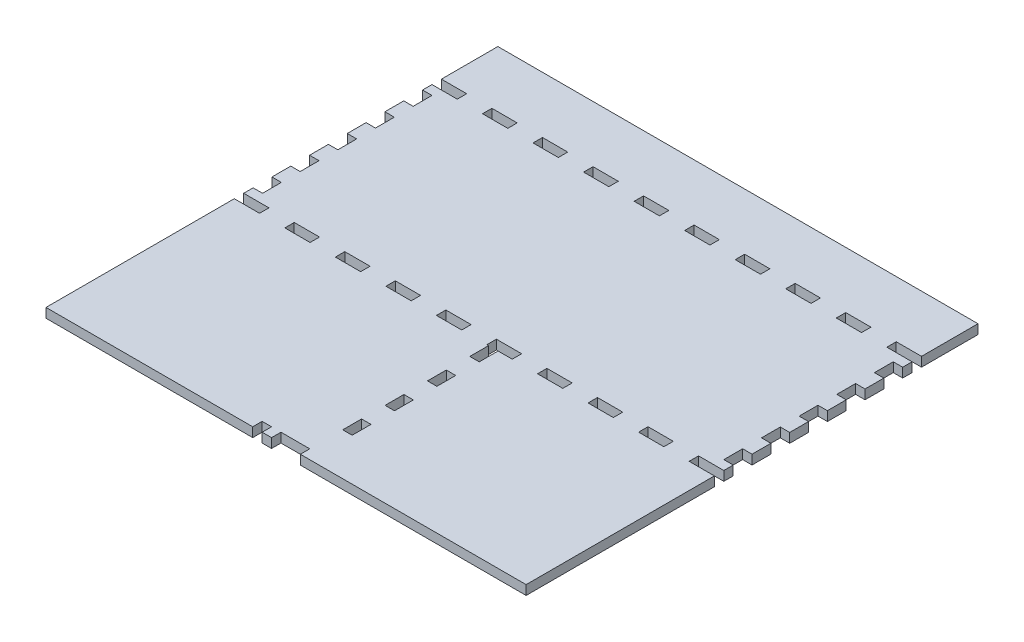
SolidWorks part; units mm, degrees
material "Acrylic (Medium-high impact)"
ref_plane "Front Plane" through (0, 0, 0) normal (0, 0, 1) x (1, 0, 0)
ref_plane "Top Plane" through (0, 0, 0) normal (0, 1, 0) x (1, 0, 0)
ref_plane "Right Plane" through (0, 0, 0) normal (1, 0, 0) x (0, 0, -1)
sketch "Sketch1" plane through (0, 0, 0) normal (0, 1, 0) x (1, 0, 0)
  line L1 (-161.925, 69.85) -> (161.925, 69.85)
  line L2 (-161.925, 69.85) -> (-161.925, -69.85)
  line L3 (-161.925, -69.85) -> (161.925, -69.85)
  line L4 (161.925, 69.85) -> (161.925, -69.85)
  point P4 (-161.925, 0)
  point P6 (0, 69.85)
  dimension "D1" = 139.7
  dimension "D2" = 323.85
extrude "Boss-Extrude1" add sketch "Sketch1" along normal blind 6.35
sketch "Sketch2" plane through (0, 6.35, 0) normal (0, 1, 0) x (1, 0, 0)
  line L0 (161.925, -69.85) -> (161.925, 69.85) construction
  line L1 (-161.925, 69.85) -> (161.925, 69.85)
  line L2 (-161.925, 69.85) -> (-161.925, -69.85)
  line L3 (-161.925, -69.85) -> (161.925, -69.85)
  line L4 (161.925, 69.85) -> (161.925, -69.85)
  line L5 (-161.925, -69.85) -> (161.925, -69.85) construction
  line L7 (-155.575, 63.5) -> (155.575, 63.5)
  line L8 (-155.575, 63.5) -> (-155.575, -63.5)
  line L9 (-155.575, -63.5) -> (155.575, -63.5)
  line L10 (155.575, 63.5) -> (155.575, -63.5)
  point P7 (-155.575, 0)
  point P14 (-161.925, 0)
  point P15 (0, -63.5)
  point P16 (0, -69.85)
  point P17 (155.575, 0)
  point P18 (161.925, 0)
  dimension "D1" = 6.35
  dimension "D2" = 6.35
extrude "Boss-Extrude2" add sketch "Sketch2" along normal blind 298.45
sketch "Sketch3" plane through (0, 0, 69.85) normal (0, 0, 1) x (1, 0, 0)
  line L0 (-50.673, 304.8) -> (-50.673, 0) construction
  line L2 (-155.575, 6.35) -> (155.575, 6.35) construction
  line L4 (-53.975, 283.21) -> (-53.975, 6.35)
  line L5 (-53.975, 6.35) -> (-47.371, 6.35)
  line L6 (-47.371, 292.354) -> (-47.371, 6.35)
  line L7 (-47.371, 292.354) -> (-66.929, 292.354)
  line L9 (-56.515, 285.75) -> (-66.929, 285.75)
  line L10 (-66.929, 292.354) -> (-66.929, 285.75)
  line L11 (-47.371, 101.6) -> (-34.671, 101.6) construction
  line L12 (-161.925, 0) -> (161.925, 0) construction
  line L13 (-37.846, 88.9) -> (-37.846, 101.6) construction
  line L14 (-41.021, 88.9) -> (-34.671, 88.9)
  line L15 (-41.021, 88.9) -> (-41.021, 71.9667)
  line L16 (-41.021, 71.9667) -> (-34.671, 71.9667)
  line L17 (-34.671, 88.9) -> (-34.671, 71.9667)
  line L18 (-41.021, 42.3333) -> (-34.671, 42.3333)
  line L19 (-41.021, 42.3333) -> (-41.021, 59.2667)
  line L20 (-41.021, 59.2667) -> (-34.671, 59.2667)
  line L21 (-34.671, 42.3333) -> (-34.671, 59.2667)
  line L26 (-41.021, 29.6333) -> (-34.671, 29.6333)
  line L27 (-41.021, 29.6333) -> (-41.021, 12.7)
  line L28 (-41.021, 12.7) -> (-34.671, 12.7)
  line L29 (-34.671, 29.6333) -> (-34.671, 12.7)
  line L30 (-37.846, 59.2667) -> (-37.846, 71.9667) construction
  line L31 (-37.846, 29.6333) -> (-37.846, 42.3333) construction
  line L32 (-37.846, 12.7) -> (-37.846, 0) construction
  line L33 (-161.925, 304.8) -> (161.925, 304.8) construction
  line L34 (-155.575, 304.8) -> (-155.575, 6.35) construction
  arc A0 (-53.975, 283.21) -> (-56.515, 285.75) centre (-56.515, 283.21) ccw
  point P5 (-50.673, 6.35)
  dimension "D5" = 2.54
  dimension "D1" = 6.604
  dimension "D2" = 12.954
  dimension "D3" = 6.604
  dimension "D4" = 286.004
  dimension "D6" = 101.6
  dimension "D7" = 12.7
  dimension "D8" = 12.7
  dimension "D9" = 6.35
  dimension "D10" = 101.6
extrude "Door Slot" cut sketch "Sketch3" against normal blind 12.7
sketch "Sketch4" plane through (0, 0, -63.5) normal (0, 0, 1) x (1, 0, 0)
  line L0 (-161.925, 304.8) -> (161.925, 304.8) construction
  line L1 (-73.279, 304.8) -> (-66.929, 304.8)
  line L2 (-73.279, 304.8) -> (-73.279, 6.35)
  line L3 (-73.279, 6.35) -> (-66.929, 6.35)
  line L4 (-66.929, 304.8) -> (-66.929, 6.35)
  line L5 (-44.196, 263.525) -> (-44.196, 247.65) construction
  line L6 (-66.929, 292.354) -> (-66.929, 285.75) construction
  line L7 (-47.371, 304.8) -> (-41.021, 304.8)
  line L8 (-47.371, 304.8) -> (-47.371, 6.35)
  line L9 (-47.371, 6.35) -> (-41.021, 6.35)
  line L10 (-41.021, 304.8) -> (-41.021, 6.35)
  line L11 (155.575, 6.35) -> (-155.575, 6.35) construction
  line L12 (-47.371, 6.35) -> (-47.371, 292.354) construction
  line L13 (-66.929, 304.8) -> (-73.279, 304.8)
  line L14 (-66.929, 304.8) -> (-66.929, 292.1)
  line L15 (-66.929, 292.1) -> (-73.279, 292.1)
  line L16 (-73.279, 304.8) -> (-73.279, 292.1)
  line L17 (-66.929, 276.225) -> (-73.279, 276.225)
  line L18 (-66.929, 276.225) -> (-66.929, 263.525)
  line L19 (-66.929, 263.525) -> (-73.279, 263.525)
  line L20 (-73.279, 276.225) -> (-73.279, 263.525)
  line L21 (-73.279, 6.35) -> (-66.929, 6.35)
  line L22 (-73.279, 6.35) -> (-73.279, 19.05)
  line L23 (-73.279, 19.05) -> (-66.929, 19.05)
  line L24 (-66.929, 6.35) -> (-66.929, 19.05)
  line L25 (-73.279, 34.925) -> (-66.929, 34.925)
  line L26 (-73.279, 34.925) -> (-73.279, 47.625)
  line L27 (-73.279, 47.625) -> (-66.929, 47.625)
  line L28 (-66.929, 34.925) -> (-66.929, 47.625)
  line L29 (-73.279, 92.075) -> (-66.929, 92.075)
  line L30 (-73.279, 92.075) -> (-73.279, 104.775)
  line L31 (-73.279, 104.775) -> (-66.929, 104.775)
  line L32 (-66.929, 92.075) -> (-66.929, 104.775)
  line L33 (-73.279, 149.225) -> (-66.929, 149.225)
  line L34 (-73.279, 149.225) -> (-73.279, 161.925)
  line L35 (-73.279, 161.925) -> (-66.929, 161.925)
  line L36 (-66.929, 149.225) -> (-66.929, 161.925)
  line L37 (-73.279, 177.8) -> (-66.929, 177.8)
  line L38 (-73.279, 177.8) -> (-73.279, 190.5)
  line L39 (-73.279, 190.5) -> (-66.929, 190.5)
  line L40 (-66.929, 177.8) -> (-66.929, 190.5)
  line L41 (-73.279, 206.375) -> (-66.929, 206.375)
  line L42 (-73.279, 206.375) -> (-73.279, 219.075)
  line L43 (-73.279, 219.075) -> (-66.929, 219.075)
  line L44 (-66.929, 206.375) -> (-66.929, 219.075)
  line L45 (-73.279, 234.95) -> (-66.929, 234.95)
  line L46 (-73.279, 234.95) -> (-73.279, 247.65)
  line L47 (-73.279, 247.65) -> (-66.929, 247.65)
  line L48 (-66.929, 234.95) -> (-66.929, 247.65)
  line L49 (-66.929, 133.35) -> (-73.279, 133.35)
  line L50 (-66.929, 133.35) -> (-66.929, 120.65)
  line L51 (-66.929, 120.65) -> (-73.279, 120.65)
  line L52 (-73.279, 133.35) -> (-73.279, 120.65)
  line L53 (-66.929, 76.2) -> (-73.279, 76.2)
  line L54 (-66.929, 76.2) -> (-66.929, 63.5)
  line L55 (-66.929, 63.5) -> (-73.279, 63.5)
  line L56 (-73.279, 76.2) -> (-73.279, 63.5)
  line L57 (-70.104, 304.8) -> (-70.104, 292.1) construction
  line L58 (-70.104, 292.1) -> (-70.104, 276.225) construction
  line L59 (-70.104, 276.225) -> (-70.104, 263.525) construction
  line L60 (-70.104, 247.65) -> (-70.104, 234.95) construction
  line L61 (-70.104, 234.95) -> (-70.104, 219.075) construction
  line L62 (-70.104, 219.075) -> (-70.104, 206.375) construction
  line L63 (-70.104, 206.375) -> (-70.104, 190.5) construction
  line L64 (-70.104, 190.5) -> (-70.104, 177.8) construction
  line L65 (-70.104, 177.8) -> (-70.104, 161.925) construction
  line L66 (-70.104, 161.925) -> (-70.104, 149.225) construction
  line L67 (-70.104, 133.35) -> (-70.104, 120.65) construction
  line L68 (-70.104, 120.65) -> (-70.104, 104.775) construction
  line L69 (-70.104, 104.775) -> (-70.104, 92.075) construction
  line L70 (-70.104, 92.075) -> (-70.104, 76.2) construction
  line L71 (-70.104, 76.2) -> (-70.104, 63.5) construction
  line L72 (-70.104, 63.5) -> (-70.104, 47.625) construction
  line L73 (-70.104, 47.625) -> (-70.104, 34.925) construction
  line L74 (-70.104, 34.925) -> (-70.104, 19.05) construction
  line L75 (-70.104, 19.05) -> (-70.104, 6.35) construction
  line L76 (-70.104, 149.225) -> (-70.104, 133.35) construction
  line L77 (-70.104, 263.525) -> (-70.104, 247.65) construction
  line L78 (-57.15, 304.8) -> (-57.15, 0) construction
  line L79 (161.925, 304.8) -> (-161.925, 304.8) construction
  line L80 (161.925, 0) -> (-161.925, 0) construction
  line L81 (-57.15, 8.3493) -> (-47.371, 8.3493) construction
  line L82 (-57.15, 8.3493) -> (-66.929, 8.3493) construction
  line L83 (-44.196, 149.225) -> (-44.196, 133.35) construction
  line L84 (-44.196, 19.05) -> (-44.196, 6.35) construction
  line L85 (-44.196, 34.925) -> (-44.196, 19.05) construction
  line L86 (-44.196, 47.625) -> (-44.196, 34.925) construction
  line L87 (-44.196, 63.5) -> (-44.196, 47.625) construction
  line L88 (-44.196, 76.2) -> (-44.196, 63.5) construction
  line L89 (-44.196, 92.075) -> (-44.196, 76.2) construction
  line L90 (-44.196, 104.775) -> (-44.196, 92.075) construction
  line L91 (-44.196, 120.65) -> (-44.196, 104.775) construction
  line L92 (-44.196, 133.35) -> (-44.196, 120.65) construction
  line L93 (-44.196, 161.925) -> (-44.196, 149.225) construction
  line L94 (-44.196, 177.8) -> (-44.196, 161.925) construction
  line L95 (-44.196, 190.5) -> (-44.196, 177.8) construction
  line L96 (-44.196, 206.375) -> (-44.196, 190.5) construction
  line L97 (-44.196, 219.075) -> (-44.196, 206.375) construction
  line L98 (-44.196, 234.95) -> (-44.196, 219.075) construction
  line L99 (-44.196, 247.65) -> (-44.196, 234.95) construction
  line L100 (-44.196, 276.225) -> (-44.196, 263.525) construction
  line L101 (-44.196, 292.1) -> (-44.196, 276.225) construction
  line L102 (-44.196, 304.8) -> (-44.196, 292.1) construction
  line L103 (-41.021, 76.2) -> (-41.021, 63.5)
  line L104 (-47.371, 63.5) -> (-41.021, 63.5)
  line L105 (-47.371, 76.2) -> (-47.371, 63.5)
  line L106 (-47.371, 76.2) -> (-41.021, 76.2)
  line L107 (-41.021, 133.35) -> (-41.021, 120.65)
  line L108 (-47.371, 120.65) -> (-41.021, 120.65)
  line L109 (-47.371, 133.35) -> (-47.371, 120.65)
  line L110 (-47.371, 133.35) -> (-41.021, 133.35)
  line L111 (-47.371, 234.95) -> (-47.371, 247.65)
  line L112 (-41.021, 247.65) -> (-47.371, 247.65)
  line L113 (-41.021, 234.95) -> (-41.021, 247.65)
  line L114 (-41.021, 234.95) -> (-47.371, 234.95)
  line L115 (-47.371, 206.375) -> (-47.371, 219.075)
  line L116 (-41.021, 219.075) -> (-47.371, 219.075)
  line L117 (-41.021, 206.375) -> (-41.021, 219.075)
  line L118 (-41.021, 206.375) -> (-47.371, 206.375)
  line L119 (-47.371, 177.8) -> (-47.371, 190.5)
  line L120 (-41.021, 190.5) -> (-47.371, 190.5)
  line L121 (-41.021, 177.8) -> (-41.021, 190.5)
  line L122 (-41.021, 177.8) -> (-47.371, 177.8)
  line L123 (-47.371, 149.225) -> (-47.371, 161.925)
  line L124 (-41.021, 161.925) -> (-47.371, 161.925)
  line L125 (-41.021, 149.225) -> (-41.021, 161.925)
  line L126 (-41.021, 149.225) -> (-47.371, 149.225)
  line L127 (-47.371, 92.075) -> (-47.371, 104.775)
  line L128 (-41.021, 104.775) -> (-47.371, 104.775)
  line L129 (-41.021, 92.075) -> (-41.021, 104.775)
  line L130 (-41.021, 92.075) -> (-47.371, 92.075)
  line L131 (-47.371, 34.925) -> (-47.371, 47.625)
  line L132 (-41.021, 47.625) -> (-47.371, 47.625)
  line L133 (-41.021, 34.925) -> (-41.021, 47.625)
  line L134 (-41.021, 34.925) -> (-47.371, 34.925)
  line L135 (-47.371, 6.35) -> (-47.371, 19.05)
  line L136 (-41.021, 19.05) -> (-47.371, 19.05)
  line L137 (-41.021, 6.35) -> (-41.021, 19.05)
  line L138 (-41.021, 6.35) -> (-47.371, 6.35)
  line L139 (-41.021, 276.225) -> (-41.021, 263.525)
  line L140 (-47.371, 263.525) -> (-41.021, 263.525)
  line L141 (-47.371, 276.225) -> (-47.371, 263.525)
  line L142 (-47.371, 276.225) -> (-41.021, 276.225)
  line L143 (-41.021, 304.8) -> (-41.021, 292.1)
  line L144 (-47.371, 292.1) -> (-41.021, 292.1)
  line L145 (-47.371, 304.8) -> (-47.371, 292.1)
  line L146 (-47.371, 304.8) -> (-41.021, 304.8)
  line L147 (-47.371, 304.8) -> (-47.371, 6.35)
  line L148 (-41.021, 6.35) -> (-47.371, 6.35)
  line L149 (-41.021, 304.8) -> (-41.021, 6.35)
  line L150 (-41.021, 304.8) -> (-47.371, 304.8)
  point P14 (-66.929, 289.052)
  dimension "D1" = 6.35
  dimension "D2" = 12.7
extrude "Door Guide Holes" cut sketch "Sketch4" against normal up to next contours L17 L4 L15 L2 | L2 L47 L4 L19 | L45 L2 L43 L4 | L41 L2 L39 L4 | L37 L2 L35 L4 | L49 L4 L33 L2 | L4 L51 L2 L31 | L53 L4 L29 L2 | L4 L55 L2 L27 | L25 L2 L23 L4 region at (-70.104, 284.1625, -63.5) region at (-70.104, 255.5875, -63.5) region at (-70.104, 227.0125, -63.5) region at (-70.104, 198.4375, -63.5) region at (-70.104, 169.8625, -63.5) region at (-70.104, 141.2875, -63.5) region at (-70.104, 112.7125, -63.5) region at (-70.104, 84.1375, -63.5) region at (-70.104, 55.5625, -63.5) region at (-70.104, 26.9875, -63.5)
ref_plane "Plane1" through (-57.15, 0, 0) normal (-1, 0, 0) x (0, 0, 1)
mirror "Mirror1" about plane through (-57.15, 0, 0) normal (-1, 0, 0) of "Door Guide Holes"
sketch "Lever Holes" plane through (0, 0, 69.85) normal (0, 0, 1) x (1, 0, 0)
  line L0 (49.276, 31.75) -> (58.928, 31.75)
  line L1 (49.276, 31.75) -> (49.276, 25.4)
  line L2 (49.276, 25.4) -> (58.928, 25.4)
  line L3 (58.928, 31.75) -> (58.928, 25.4)
  line L4 (36.1315, 19.05) -> (42.4815, 19.05)
  line L5 (36.1315, 19.05) -> (36.1315, 12.7)
  line L6 (36.1315, 12.7) -> (42.4815, 12.7)
  line L7 (42.4815, 19.05) -> (42.4815, 12.7)
  line L8 (65.7225, 19.05) -> (72.0725, 19.05)
  line L9 (65.7225, 19.05) -> (65.7225, 12.7)
  line L10 (65.7225, 12.7) -> (72.0725, 12.7)
  line L11 (72.0725, 19.05) -> (72.0725, 12.7)
  line L12 (42.4815, 15.875) -> (65.7225, 15.875) construction
  line L13 (-161.925, 0) -> (161.925, 0) construction
  line L14 (-47.371, 6.35) -> (155.575, 6.35) construction
  line L15 (155.575, 6.35) -> (-155.575, 6.35) construction
  point P12 (54.102, 15.875)
  point P13 (54.102, 25.4)
  point P24 (54.102, 6.35)
  dimension "D1" = 9.652
  dimension "D2" = 6.35
  dimension "D3" = 6.35
  dimension "D4" = 6.35
  dimension "D5" = 23.241
  dimension "D6" = 25.4
  dimension "D7" = 12.7
extrude "Cut-Extrude1" cut sketch "Lever Holes" against normal through all
sketch "Sketch7" plane through (161.925, 0, 0) normal (1, 0, 0) x (0, 0, -1)
  line L0 (-37.211, 92.583) -> (37.211, 92.583)
  line L1 (-37.211, 92.583) -> (-37.211, 18.161)
  line L2 (-37.211, 18.161) -> (37.211, 18.161)
  line L3 (37.211, 92.583) -> (37.211, 18.161)
  line L4 (-69.85, 0) -> (69.85, 0) construction
  circle A0 centre (0, 55.372) radius 26.9875
  circle A1 centre (-37.211, 92.583) radius 3.175
  circle A2 centre (37.211, 92.583) radius 3.175
  circle A3 centre (-37.211, 18.161) radius 3.175
  circle A4 centre (37.211, 18.161) radius 3.175
  point P9 (0, 18.161)
  point P10 (-37.211, 55.372)
  dimension "D3" = 53.975
  dimension "D4" = 6.35
  dimension "D1" = 74.422
  dimension "D2" = 55.372
extrude "Cut-Extrude2" cut sketch "Sketch7" against normal up to next contours A0 | L0 A1 L1 | L1 A1 L0 | L3 A2 L0 | L0 A2 L3 | L2 A3 L1 | L1 A3 L2 | L2 A4 L3 | L3 A4 L2 region at (161.925, 93.0322, 37.6602) region at (161.925, 91.2355, 35.8635) region at (161.925, 93.0322, -37.6602) region at (161.925, 91.2355, -35.8635) region at (161.925, 19.5085, 35.8635) region at (161.925, 17.7118, 37.6602) region at (161.925, 17.7118, -37.6602) region at (161.925, 19.5085, -35.8635) region at (161.925, 55.372, 0)
sketch "Sketch8" plane through (-161.925, 0, 0) normal (-1, 0, 0) x (0, 0, 1)
  line L0 (-69.85, 0) -> (69.85, 0) construction
  circle A0 centre (0, 19.05) radius 3.175
  point P6 (0, 0)
  dimension "D1" = 6.35
  dimension "D2" = 19.05
extrude "Cut-Extrude3" cut sketch "Sketch8" against normal up to next
sketch "Sketch10" plane through (0, 0, 0) normal (0, -1, 0) x (1, 0, 0)
  line L0 (-155.575, 63.5) -> (155.575, 63.5) construction
  line L1 (-161.925, 69.85) -> (-144.8803, 69.85)
  line L2 (-161.925, 69.85) -> (-161.925, 63.5)
  line L3 (-161.925, 63.5) -> (-144.8803, 63.5)
  line L4 (-144.8803, 69.85) -> (-144.8803, 63.5)
  line L5 (-144.8803, 69.85) -> (-127.8355, 69.85)
  line L6 (-144.8803, 69.85) -> (-144.8803, 63.5)
  line L7 (-144.8803, 63.5) -> (-127.8355, 63.5)
  line L8 (-127.8355, 69.85) -> (-127.8355, 63.5)
  line L9 (-127.8355, 69.85) -> (-110.7908, 69.85)
  line L10 (-127.8355, 69.85) -> (-127.8355, 63.5)
  line L11 (-127.8355, 63.5) -> (-110.7908, 63.5)
  line L12 (-110.7908, 69.85) -> (-110.7908, 63.5)
  line L13 (-110.7908, 69.85) -> (-93.7461, 69.85)
  line L14 (-110.7908, 69.85) -> (-110.7908, 63.5)
  line L15 (-110.7908, 63.5) -> (-93.7461, 63.5)
  line L16 (-93.7461, 69.85) -> (-93.7461, 63.5)
  line L17 (-161.925, 69.85) -> (161.925, 69.85) construction
  line L18 (-66.929, 63.5) -> (-47.371, 63.5) construction
  line L19 (-93.7461, 69.85) -> (-76.7013, 69.85)
  line L20 (-93.7461, 69.85) -> (-93.7461, 63.5)
  line L21 (-93.7461, 63.5) -> (-76.7013, 63.5)
  line L22 (-76.7013, 69.85) -> (-76.7013, 63.5)
  line L23 (-76.7013, 69.85) -> (-59.6566, 69.85)
  line L24 (-76.7013, 69.85) -> (-76.7013, 63.5)
  line L25 (-76.7013, 63.5) -> (-59.6566, 63.5)
  line L26 (-59.6566, 69.85) -> (-59.6566, 63.5)
  line L27 (-59.6566, 69.85) -> (-42.6118, 69.85)
  line L28 (-59.6566, 69.85) -> (-59.6566, 63.5)
  line L29 (-59.6566, 63.5) -> (-42.6118, 63.5)
  line L30 (-42.6118, 69.85) -> (-42.6118, 63.5)
  line L31 (-42.6118, 69.85) -> (-25.5671, 69.85)
  line L32 (-42.6118, 69.85) -> (-42.6118, 63.5)
  line L33 (-42.6118, 63.5) -> (-25.5671, 63.5)
  line L34 (-25.5671, 69.85) -> (-25.5671, 63.5)
  line L36 (-25.5671, 69.85) -> (-8.5224, 69.85)
  line L37 (-25.5671, 69.85) -> (-25.5671, 63.5)
  line L38 (-25.5671, 63.5) -> (-8.5224, 63.5)
  line L39 (-8.5224, 69.85) -> (-8.5224, 63.5)
  line L40 (-8.5224, 69.85) -> (8.5224, 69.85)
  line L41 (-8.5224, 69.85) -> (-8.5224, 63.5)
  line L42 (-8.5224, 63.5) -> (8.5224, 63.5)
  line L43 (8.5224, 69.85) -> (8.5224, 63.5)
  line L44 (8.5224, 69.85) -> (25.5671, 69.85)
  line L45 (8.5224, 69.85) -> (8.5224, 63.5)
  line L46 (8.5224, 63.5) -> (25.5671, 63.5)
  line L47 (25.5671, 69.85) -> (25.5671, 63.5)
  line L48 (25.5671, 69.85) -> (42.6118, 69.85)
  line L49 (25.5671, 69.85) -> (25.5671, 63.5)
  line L50 (25.5671, 63.5) -> (42.6118, 63.5)
  line L51 (42.6118, 69.85) -> (42.6118, 63.5)
  line L52 (42.6118, 69.85) -> (59.6566, 69.85)
  line L53 (42.6118, 69.85) -> (42.6118, 63.5)
  line L54 (42.6118, 63.5) -> (59.6566, 63.5)
  line L55 (59.6566, 69.85) -> (59.6566, 63.5)
  line L56 (59.6566, 69.85) -> (76.7013, 69.85)
  line L57 (59.6566, 69.85) -> (59.6566, 63.5)
  line L58 (59.6566, 63.5) -> (76.7013, 63.5)
  line L59 (76.7013, 69.85) -> (76.7013, 63.5)
  line L60 (76.7013, 69.85) -> (93.7461, 69.85)
  line L61 (76.7013, 69.85) -> (76.7013, 63.5)
  line L62 (76.7013, 63.5) -> (93.7461, 63.5)
  line L63 (93.7461, 69.85) -> (93.7461, 63.5)
  line L64 (93.7461, 69.85) -> (110.7908, 69.85)
  line L65 (93.7461, 69.85) -> (93.7461, 63.5)
  line L66 (93.7461, 63.5) -> (110.7908, 63.5)
  line L67 (110.7908, 69.85) -> (110.7908, 63.5)
  line L68 (110.7908, 69.85) -> (127.8355, 69.85)
  line L69 (110.7908, 69.85) -> (110.7908, 63.5)
  line L70 (110.7908, 63.5) -> (127.8355, 63.5)
  line L71 (127.8355, 69.85) -> (127.8355, 63.5)
  line L72 (127.8355, 69.85) -> (144.8803, 69.85)
  line L73 (127.8355, 69.85) -> (127.8355, 63.5)
  line L74 (127.8355, 63.5) -> (144.8803, 63.5)
  line L75 (144.8803, 69.85) -> (144.8803, 63.5)
  line L76 (-155.575, -63.5) -> (-155.575, 63.5) construction
  line L77 (-161.925, 69.85) -> (-155.575, 69.85)
  line L78 (-161.925, 69.85) -> (-161.925, 57.15)
  line L79 (-161.925, 57.15) -> (-155.575, 57.15)
  line L80 (-155.575, 69.85) -> (-155.575, 57.15)
  line L82 (-161.925, 57.15) -> (-155.575, 57.15)
  line L83 (-161.925, 57.15) -> (-161.925, 44.45)
  line L84 (-161.925, 44.45) -> (-155.575, 44.45)
  line L85 (-155.575, 57.15) -> (-155.575, 44.45)
  line L86 (-161.925, 44.45) -> (-155.575, 44.45)
  line L87 (-161.925, 44.45) -> (-161.925, 31.75)
  line L88 (-161.925, 31.75) -> (-155.575, 31.75)
  line L89 (-155.575, 44.45) -> (-155.575, 31.75)
  line L90 (-161.925, 31.75) -> (-155.575, 31.75)
  line L91 (-161.925, 31.75) -> (-161.925, 19.05)
  line L92 (-161.925, 19.05) -> (-155.575, 19.05)
  line L93 (-155.575, 31.75) -> (-155.575, 19.05)
  line L94 (-161.925, 19.05) -> (-155.575, 19.05)
  line L95 (-161.925, 19.05) -> (-161.925, 6.35)
  line L96 (-161.925, 6.35) -> (-155.575, 6.35)
  line L97 (-155.575, 19.05) -> (-155.575, 6.35)
  line L98 (-161.925, 6.35) -> (-155.575, 6.35)
  line L99 (-161.925, 6.35) -> (-161.925, -6.35)
  line L100 (-161.925, -6.35) -> (-155.575, -6.35)
  line L101 (-155.575, 6.35) -> (-155.575, -6.35)
  line L102 (-161.925, -6.35) -> (-155.575, -6.35)
  line L103 (-161.925, -6.35) -> (-161.925, -19.05)
  line L104 (-161.925, -19.05) -> (-155.575, -19.05)
  line L105 (-155.575, -6.35) -> (-155.575, -19.05)
  line L106 (-161.925, -19.05) -> (-155.575, -19.05)
  line L107 (-161.925, -19.05) -> (-161.925, -31.75)
  line L108 (-161.925, -31.75) -> (-155.575, -31.75)
  line L109 (-155.575, -19.05) -> (-155.575, -31.75)
  line L110 (-161.925, -31.75) -> (-155.575, -31.75)
  line L111 (-161.925, -31.75) -> (-161.925, -44.45)
  line L112 (-161.925, -44.45) -> (-155.575, -44.45)
  line L113 (-155.575, -31.75) -> (-155.575, -44.45)
  line L114 (-161.925, -44.45) -> (-155.575, -44.45)
  line L115 (-161.925, -44.45) -> (-161.925, -57.15)
  line L116 (-161.925, -57.15) -> (-155.575, -57.15)
  line L117 (-155.575, -44.45) -> (-155.575, -57.15)
  line L118 (161.925, 69.85) -> (161.925, -69.85) construction
  line L119 (144.8803, 69.85) -> (161.925, 69.85)
  line L120 (144.8803, 69.85) -> (144.8803, 63.5)
  line L121 (144.8803, 63.5) -> (161.925, 63.5)
  line L122 (161.925, 69.85) -> (161.925, 63.5)
  line L123 (161.925, -69.85) -> (-161.925, -69.85) construction
  line L124 (-161.925, -57.15) -> (-155.575, -57.15)
  line L125 (-161.925, -57.15) -> (-161.925, -69.85)
  line L126 (-161.925, -69.85) -> (-155.575, -69.85)
  line L127 (-155.575, -57.15) -> (-155.575, -69.85)
  line L128 (55, 0) -> (-55, 0) construction
  line L129 (161.925, -69.85) -> (161.925, -63.5)
  line L130 (144.8803, -63.5) -> (161.925, -63.5)
  line L131 (144.8803, -69.85) -> (161.925, -69.85)
  line L132 (144.8803, -69.85) -> (144.8803, -63.5)
  line L133 (127.8355, -63.5) -> (144.8803, -63.5)
  line L134 (127.8355, -69.85) -> (144.8803, -69.85)
  line L135 (127.8355, -69.85) -> (127.8355, -63.5)
  line L136 (110.7908, -63.5) -> (127.8355, -63.5)
  line L137 (110.7908, -69.85) -> (127.8355, -69.85)
  line L138 (110.7908, -69.85) -> (110.7908, -63.5)
  line L139 (93.7461, -63.5) -> (110.7908, -63.5)
  line L140 (93.7461, -69.85) -> (110.7908, -69.85)
  line L141 (93.7461, -69.85) -> (93.7461, -63.5)
  line L142 (76.7013, -63.5) -> (93.7461, -63.5)
  line L143 (76.7013, -69.85) -> (93.7461, -69.85)
  line L144 (59.6566, -63.5) -> (76.7013, -63.5)
  line L145 (76.7013, -69.85) -> (76.7013, -63.5)
  line L146 (59.6566, -69.85) -> (76.7013, -69.85)
  line L147 (59.6566, -69.85) -> (59.6566, -63.5)
  line L148 (42.6118, -63.5) -> (59.6566, -63.5)
  line L149 (42.6118, -69.85) -> (59.6566, -69.85)
  line L150 (42.6118, -69.85) -> (42.6118, -63.5)
  line L151 (25.5671, -63.5) -> (42.6118, -63.5)
  line L152 (25.5671, -69.85) -> (42.6118, -69.85)
  line L153 (25.5671, -69.85) -> (25.5671, -63.5)
  line L154 (8.5224, -69.85) -> (25.5671, -69.85)
  line L155 (8.5224, -63.5) -> (25.5671, -63.5)
  line L156 (8.5224, -69.85) -> (8.5224, -63.5)
  line L157 (-8.5224, -63.5) -> (8.5224, -63.5)
  line L158 (-8.5224, -69.85) -> (8.5224, -69.85)
  line L159 (-25.5671, -63.5) -> (-8.5224, -63.5)
  line L160 (-8.5224, -69.85) -> (-8.5224, -63.5)
  line L161 (-25.5671, -69.85) -> (-8.5224, -69.85)
  line L162 (-25.5671, -69.85) -> (-25.5671, -63.5)
  line L163 (-42.6118, -63.5) -> (-25.5671, -63.5)
  line L164 (-42.6118, -69.85) -> (-25.5671, -69.85)
  line L165 (-42.6118, -69.85) -> (-42.6118, -63.5)
  line L166 (-59.6566, -63.5) -> (-42.6118, -63.5)
  line L167 (-59.6566, -69.85) -> (-42.6118, -69.85)
  line L168 (-59.6566, -69.85) -> (-59.6566, -63.5)
  line L169 (-76.7013, -69.85) -> (-59.6566, -69.85)
  line L170 (-76.7013, -63.5) -> (-59.6566, -63.5)
  line L171 (-93.7461, -63.5) -> (-76.7013, -63.5)
  line L172 (-76.7013, -69.85) -> (-76.7013, -63.5)
  line L173 (-93.7461, -69.85) -> (-76.7013, -69.85)
  line L174 (-110.7908, -69.85) -> (-93.7461, -69.85)
  line L175 (-110.7908, -63.5) -> (-93.7461, -63.5)
  line L176 (-93.7461, -69.85) -> (-93.7461, -63.5)
  line L177 (-127.8355, -69.85) -> (-127.8355, -63.5)
  line L178 (-127.8355, -69.85) -> (-110.7908, -69.85)
  line L179 (-110.7908, -69.85) -> (-110.7908, -63.5)
  line L180 (-127.8355, -63.5) -> (-110.7908, -63.5)
  line L181 (-144.8803, -63.5) -> (-127.8355, -63.5)
  line L182 (-144.8803, -69.85) -> (-127.8355, -69.85)
  line L183 (-144.8803, -69.85) -> (-144.8803, -63.5)
  line L184 (-161.925, -69.85) -> (-144.8803, -69.85)
  line L185 (-161.925, -69.85) -> (-161.925, -63.5)
  line L186 (-161.925, -63.5) -> (-144.8803, -63.5)
  line L187 (0, -55) -> (0, 55) construction
  line L188 (161.925, -69.85) -> (155.575, -69.85)
  line L189 (155.575, -57.15) -> (155.575, -69.85)
  line L190 (161.925, -57.15) -> (161.925, -69.85)
  line L191 (161.925, -57.15) -> (155.575, -57.15)
  line L192 (155.575, -44.45) -> (155.575, -57.15)
  line L193 (161.925, -44.45) -> (161.925, -57.15)
  line L194 (161.925, -44.45) -> (155.575, -44.45)
  line L195 (155.575, -31.75) -> (155.575, -44.45)
  line L196 (161.925, -31.75) -> (161.925, -44.45)
  line L197 (161.925, -31.75) -> (155.575, -31.75)
  line L198 (161.925, -19.05) -> (161.925, -31.75)
  line L199 (155.575, -19.05) -> (155.575, -31.75)
  line L200 (155.575, -6.35) -> (155.575, -19.05)
  line L201 (161.925, -6.35) -> (161.925, -19.05)
  line L202 (161.925, -19.05) -> (155.575, -19.05)
  line L203 (161.925, -6.35) -> (155.575, -6.35)
  line L204 (155.575, 6.35) -> (155.575, -6.35)
  line L205 (161.925, 6.35) -> (161.925, -6.35)
  line L206 (161.925, 6.35) -> (155.575, 6.35)
  line L207 (155.575, 19.05) -> (155.575, 6.35)
  line L208 (161.925, 19.05) -> (161.925, 6.35)
  line L209 (161.925, 19.05) -> (155.575, 19.05)
  line L210 (161.925, 31.75) -> (155.575, 31.75)
  line L211 (161.925, 44.45) -> (155.575, 44.45)
  line L212 (161.925, 57.15) -> (155.575, 57.15)
  line L213 (155.575, 31.75) -> (155.575, 19.05)
  line L214 (161.925, 31.75) -> (161.925, 19.05)
  line L215 (155.575, 44.45) -> (155.575, 31.75)
  line L216 (161.925, 44.45) -> (161.925, 31.75)
  line L217 (155.575, 57.15) -> (155.575, 44.45)
  line L218 (161.925, 57.15) -> (161.925, 44.45)
  line L219 (155.575, 69.85) -> (155.575, 57.15)
  line L220 (161.925, 69.85) -> (161.925, 57.15)
  line M28 (-161.925, 69.85) -> (-161.925, -69.85)
  line M29 (-161.925, -69.85) -> (161.925, -69.85)
  line M30 (161.925, -69.85) -> (161.925, 69.85)
  line M31 (161.925, 69.85) -> (-161.925, 69.85)
sketch "Sketch9" plane through (0, 0, -69.85) normal (0, 0, -1) x (-1, 0, 0)
  line L0 (161.925, 304.8) -> (161.925, 0) construction
  line L1 (-161.925, 304.8) -> (161.925, 304.8)
  line L2 (-161.925, 304.8) -> (-161.925, 6.35)
  line L3 (-161.925, 6.35) -> (161.925, 6.35)
  line L4 (161.925, 304.8) -> (161.925, 6.35)
  line L5 (-155.575, 6.35) -> (155.575, 6.35) construction
extrude "Cut-Extrude4" cut sketch "Sketch9" against normal through all
extrude "Cut-Extrude6" cut sketch "Sketch10" against normal through all contours L80 L3 L4 M31 | L80 L1 L3 M28 | L12 L8 L11 M31 | L22 L16 L21 M31 | L30 L26 L29 M31 | L39 L34 L38 M31 | L47 L43 L46 M31 | L55 L51 L54 M31 | L63 L59 L62 M31 | L71 L67 L70 M31 | L219 L119 L75 L121 | L219 L121 M31 M30 | L212 L217 L211 M30 | L210 L213 L209 M30 | L206 L204 L203 M30 | L202 L199 L197 M30 | L194 L192 L191 M30 | L130 L189 L131 M30 | L189 L130 L132 M29 | L138 L135 L136 M29 | L145 L141 L142 M29 | L150 L147 L148 M29 | L156 L153 L155 M29 | L162 L160 L159 M29 | L168 L165 L166 M29 | L176 L172 L171 M29 | L180 L177 L179 M29 | L186 L125 L127 M29 | L186 L127 L183 M29 | L117 L112 L116 M28 | L109 L104 L108 M28 | L101 L96 L100 M28 | L93 L88 L92 M28 | L85 L79 L84 M28 region at (-158.75, 0, 66.675) region at (-150.2276, 0, 66.675) region at (-158.75, 0, 50.8) region at (-119.3132, 0, 66.675) region at (-158.75, 0, 25.4) region at (-85.2237, 0, 66.675) region at (-158.75, 0, 0) region at (-51.1342, 0, 66.675) region at (-158.75, 0, -25.4) region at (-17.0447, 0, 66.675) region at (-158.75, 0, -50.8) region at (17.0447, 0, 66.675) region at (-158.75, 0, -66.675) region at (51.1342, 0, 66.675) region at (-150.2276, 0, -66.675) region at (85.2237, 0, 66.675) region at (-119.3132, 0, -66.675) region at (119.3132, 0, 66.675) region at (-85.2237, 0, -66.675) region at (150.2276, 0, 66.675) region at (-51.1342, 0, -66.675) region at (158.75, 0, 66.675) region at (-17.0447, 0, -66.675) region at (158.75, 0, 50.8) region at (17.0447, 0, -66.675) region at (158.75, 0, 25.4) region at (51.1342, 0, -66.675) region at (158.75, 0, 0) region at (85.2237, 0, -66.675) region at (158.75, 0, -25.4) region at (119.3132, 0, -66.675) region at (158.75, 0, -50.8) region at (150.2276, 0, -66.675) region at (158.75, 0, -66.675)
sketch "Sketch12" plane through (0, 0, 0) normal (0, -1, 0) x (-1, 0, 0)
  line L0 (161.925, -196.85) -> (161.925, -69.85)
  line L1 (161.925, -69.85) -> (-161.925, -69.85)
  line L2 (-161.925, -69.85) -> (-161.925, -196.85)
  line L3 (-161.925, -196.85) -> (161.925, -196.85)
  line L4 (-127.8355, -69.85) -> (-144.8803, -69.85) construction
  line L5 (-12.827, -139.7) -> (-12.827, -155.575) construction
  line L6 (-9.652, -69.85) -> (-16.002, -69.85)
  line L7 (-9.652, -69.85) -> (-9.652, -82.55)
  line L8 (-9.652, -82.55) -> (-16.002, -82.55)
  line L9 (-16.002, -69.85) -> (-16.002, -82.55)
  line L10 (-9.652, -98.425) -> (-16.002, -98.425)
  line L11 (-9.652, -98.425) -> (-9.652, -111.125)
  line L12 (-9.652, -111.125) -> (-16.002, -111.125)
  line L13 (-16.002, -98.425) -> (-16.002, -111.125)
  line L14 (-9.652, -127) -> (-16.002, -127)
  line L15 (-9.652, -127) -> (-9.652, -139.7)
  line L16 (-9.652, -139.7) -> (-16.002, -139.7)
  line L17 (-16.002, -127) -> (-16.002, -139.7)
  line L18 (-9.652, -155.575) -> (-16.002, -155.575)
  line L19 (-9.652, -155.575) -> (-9.652, -168.275)
  line L20 (-9.652, -168.275) -> (-16.002, -168.275)
  line L21 (-16.002, -155.575) -> (-16.002, -168.275)
  line L22 (-12.827, -82.55) -> (-12.827, -98.425) construction
  line L23 (-12.827, -111.125) -> (-12.827, -127) construction
  line L24 (127.8355, 69.85) -> (144.8803, 69.85) construction
  line L25 (-9.652, -196.85) -> (9.779, -196.85)
  line L26 (-9.652, -196.85) -> (-9.652, -190.5)
  line L27 (-9.652, -190.5) -> (9.779, -190.5)
  line L28 (9.779, -196.85) -> (9.779, -190.5)
  line L29 (16.129, -196.85) -> (22.479, -196.85)
  line L30 (16.129, -196.85) -> (16.129, -190.5)
  line L31 (16.129, -190.5) -> (22.479, -190.5)
  line L32 (22.479, -196.85) -> (22.479, -190.5)
  line L33 (161.925, 69.85) -> (-161.925, 69.85)
  line L34 (161.925, 69.85) -> (161.925, 107.95)
  line L35 (161.925, 107.95) -> (-161.925, 107.95)
  line L36 (-161.925, 69.85) -> (-161.925, 107.95)
  dimension "D1" = 127
  dimension "D2" = 15.875
  dimension "D3" = 145.923
  dimension "D4" = 6.35
  dimension "D5" = 12.7
  dimension "D6" = 6.35
  dimension "D7" = 19.431
  dimension "D8" = 6.35
  dimension "D9" = 6.35
  dimension "D10" = 6.35
  dimension "D11" = 38.1
extrude "Boss-Extrude3" add sketch "Sketch12" against normal up to surface (6.35 mm away) contours L9 L1 L2 L3 L0 L7 L8 L21 L18 L19 L20 L17 L14 L15 L16 L13 L10 L11 L12 | L36 L33 L34 L35 region at (-0.0825, 0, 133.2204) region at (0, 0, -88.9) up to face at (0, 6.35, 0)
